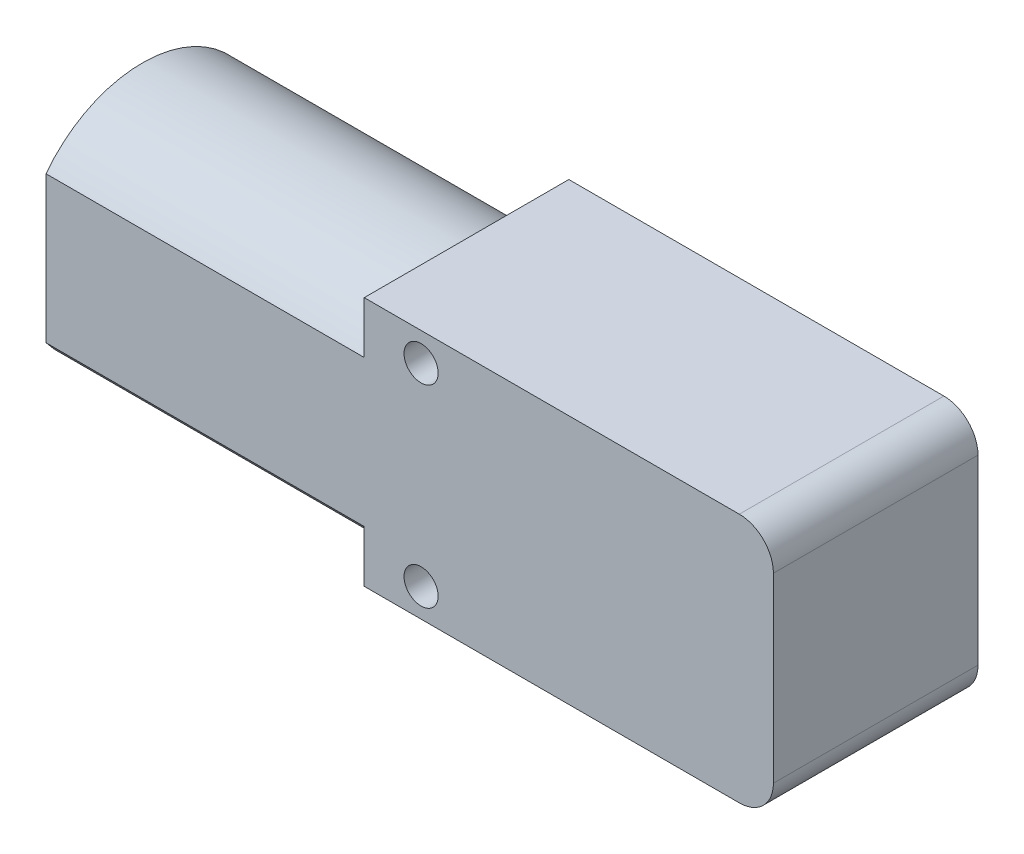
SolidWorks part; units mm, degrees
ref_plane "Piano frontale" through (0, 0, 0) normal (0, 0, 1) x (1, 0, 0)
ref_plane "Piano superiore" through (0, 0, 0) normal (0, 1, 0) x (1, 0, 0)
ref_plane "Piano destro" through (0, 0, 0) normal (1, 0, 0) x (0, 0, -1)
sketch "Schizzo1" plane through (0, 0, 0) normal (0, 0, 1) x (1, 0, 0)
  line L1 (18, 11) -> (-18, 11)
  line L2 (18, 11) -> (18, -11)
  line L3 (18, -11) -> (-18, -11)
  line L4 (-18, 11) -> (-18, -11)
  line L5 (18, 11) -> (-18, -11) construction
  line L6 (18, -11) -> (-18, 11) construction
  point P0 (0, 0)
  dimension "D1" = 22
  dimension "D2" = 36
extrude "Estrusione-Estrusione1" add sketch "Schizzo1" along normal blind 18
fillet "Raccordo1" radius 3 2 edges at (18, -11, 9) (18, 11, 9)
sketch "Schizzo2" plane through (-18, 0, 0) normal (-1, 0, 0) x (0, 0, 1)
  line L0 (1.5, 7) -> (1.5, -7)
  line L1 (18, 6.439) -> (18, -6.439)
  line L2 (0, 11) -> (0, -11) construction
  line L4 (-4.7632, 0) -> (23.8063, 0) construction
  arc A1 (1.5, 7) -> (18, 6.439) centre (9.5216, 0) cw
  arc A2 (1.5, -7) -> (18, -6.439) centre (9.5216, 0) ccw
  point P6 (1.5, 0)
  dimension "D1" = 14
  dimension "D2" = 1.5
extrude "Estrusione-Estrusione2" add sketch "Schizzo2" along normal blind 28
sketch "Schizzo3" plane through (0, 0, 0) normal (0, 0, -1) x (-1, 0, 0)
  line L0 (-18, -8) -> (-18, 8) construction
  line L1 (-29.0837, 0) -> (20.9733, 0) construction
  line L2 (18, 6.439) -> (18, 10.6464) construction
  line L3 (-15, 11) -> (18, 11) construction
  circle A0 centre (-6, 0) radius 2.5
  circle A1 centre (13, 8.5) radius 1.5
  circle A2 centre (13, -8.5) radius 1.5
  dimension "D2" = 5
  dimension "D3" = 3
  dimension "D1" = 12
  dimension "D4" = 5
  dimension "D5" = 2.5
extrude "Estrusione-Estrusione3" add sketch "Schizzo3" along normal blind 8 contours A0
extrude "Taglio-Estrusione1" cut sketch "Schizzo3<4>" against normal through all contours A1 | A2 region at (-13, 8.5, 0) region at (-13, -8.5, 0)
sketch "Schizzo3<4>" plane through (0, 0, 0) normal (0, 0, -1) x (-1, 0, 0) same geometry as "Schizzo3"
